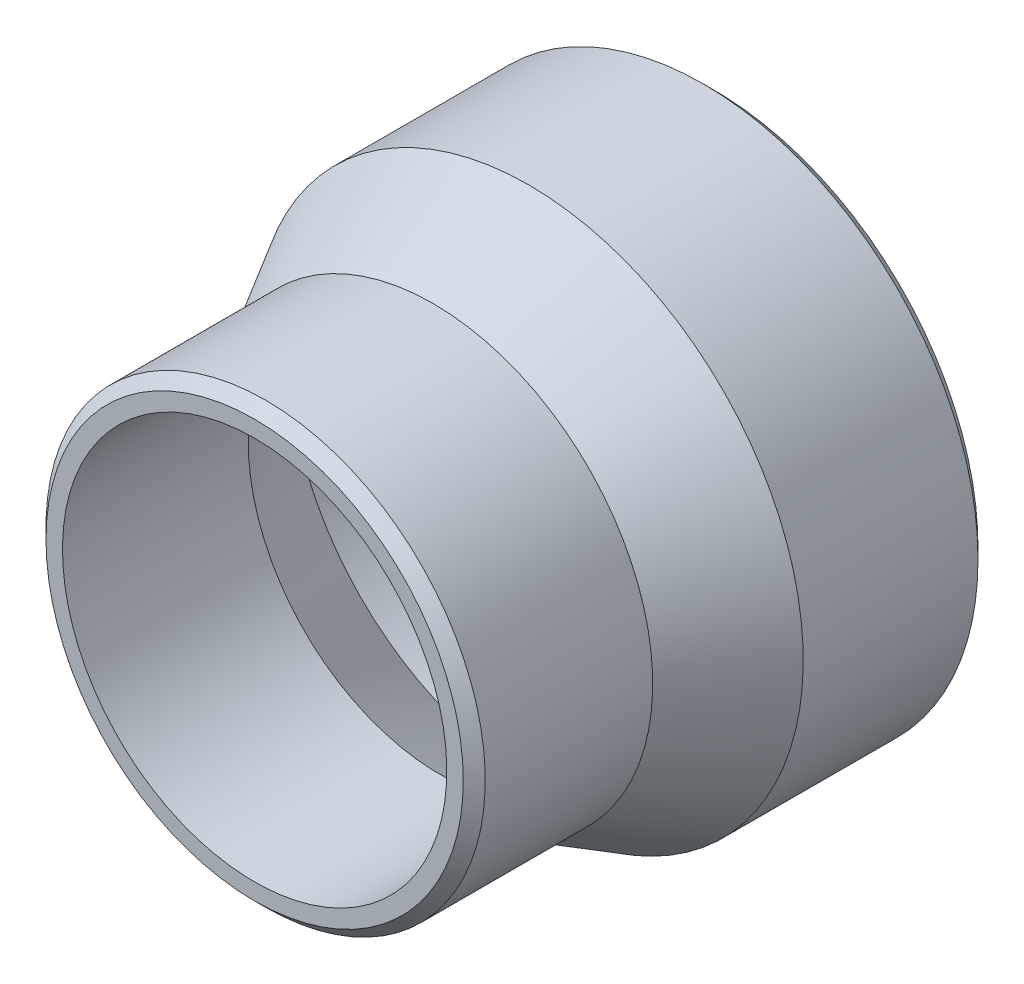
SolidWorks part; units mm, degrees
ref_plane "Pipe2 Plane" through (0, 0, 0) normal (0, 0, 1) x (1, 0, 0)
ref_plane "Top Plane" through (0, 0, 0) normal (0, 1, 0) x (1, 0, 0)
ref_plane "Right Plane" through (0, 0, 0) normal (1, 0, 0) x (0, 0, -1)
sketch "Sketch1" plane through (0, 0, 0) normal (1, 0, 0) x (0, 0, -1)
  line L0 (0, 0) -> (-106.3625, 0) construction
  line L1 (-106.3625, 0) -> (-106.3625, 50.8) construction
  line L2 (-106.3625, 50.8) -> (-65.0875, 50.8)
  line L3 (-65.0875, 50.8) -> (-42.9683, 63.5)
  line L4 (-42.9683, 63.5) -> (0, 63.5)
  line L5 (0, 63.5) -> (0, 0) construction
  line L6 (0, 63.5) -> (0, 57.15)
  line L7 (0, 57.15) -> (-41.275, 57.15)
  line L8 (-41.275, 57.15) -> (-63.3942, 44.45)
  line L9 (-63.3942, 44.45) -> (-106.3625, 44.45)
  line L10 (-106.3625, 44.45) -> (-106.3625, 50.8)
  line L11 (-65.0875, 50.8) -> (-65.0875, 0) construction
  line L12 (-41.275, 57.15) -> (-41.275, 0) construction
  line L13 (-65.0875, 25.4) -> (-41.275, 25.4) construction
  line L14 (-53.1812, 25.4) -> (-53.1812, 0) construction
  point P14 (-53.1812, 25.4)
  point P15 (-53.1812, 0)
  dimension "H" = 106.3625
  dimension "WallThickness" = 6.35
  dimension "PipeOD1" = 88.9
  dimension "D1" = 6.35
  dimension "N" = 23.8125
  dimension "PipeID2" = 114.3
revolve "Revolve1" add sketch "Sketch1" angle 360 about L0 region at (0, 53.975, 53.1812)
chamfer "Chamfer1" distance 2.54 angle 45 2 edges at (0, 63.5, 0) (0, 50.8, 106.3625)
ref_plane "Pipe1 Plane" through (0, 0, 106.3625) normal (0, 0, 1) x (1, 0, 0)
other "CPoint1" parameters "Diameter"=76.2, "StubLength"=76.2
ref_axis "Axis1" through (0, 0, 116.3625) along (0, 0, -1)
other "CPoint2" parameters "Diameter"=101.6, "StubLength"=114.3
ref_axis "Axis2" through (0, 0, -10) along (0, 0, 1)
other "RPoint1"
equation "\"D1@Sketch1\"=\"WallThickness@Sketch1\""
